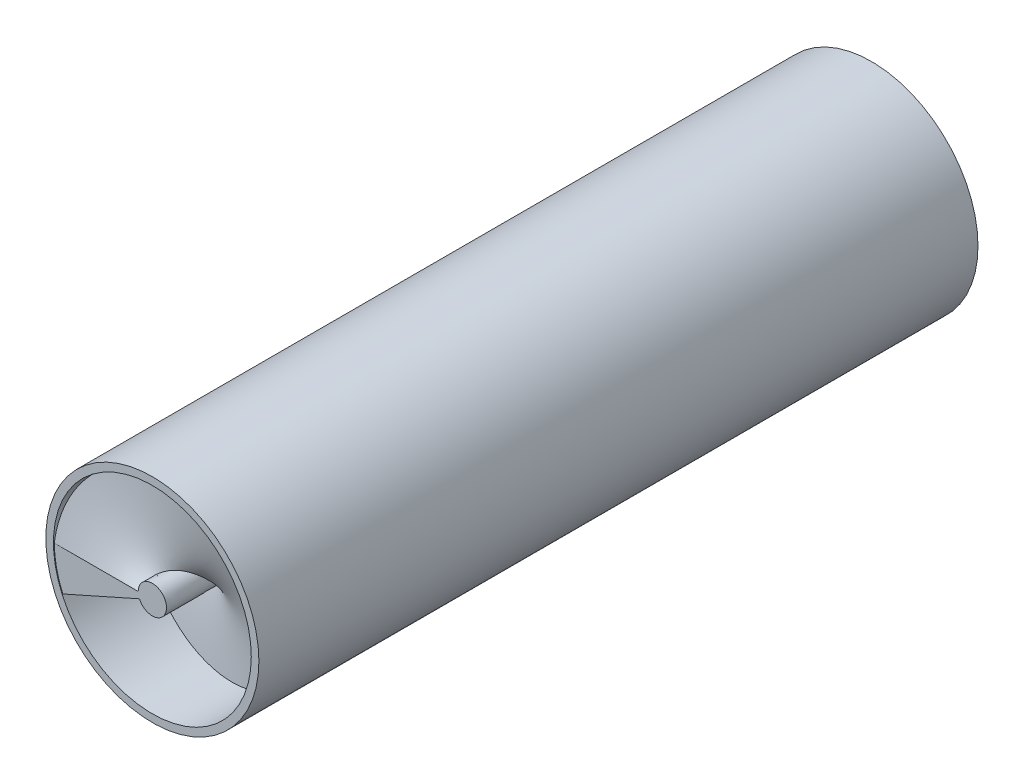
SolidWorks part; units mm, degrees
material "Custom Plastic"
ref_plane "Front Plane" through (0, 0, 0) normal (0, 0, 1) x (1, 0, 0)
ref_plane "Top Plane" through (0, 0, 0) normal (0, 1, 0) x (1, 0, 0)
ref_plane "Right Plane" through (0, 0, 0) normal (1, 0, 0) x (0, 0, -1)
sketch "Sketch2" plane through (0, 0, 0) normal (0, 0, 1) x (1, 0, 0)
  circle A0 centre (0, 0) radius 41.275
  circle A1 centre (0, 0) radius 44.45
  dimension "D1" = 82.55
  dimension "D3" = 88.9
  dimension "D2" = 3.175
extrude "Boss-Extrude2" add sketch "Sketch2" along normal blind 300
sketch "Sketch3" plane through (0, 0, 0) normal (0, 0, 1) x (1, 0, 0)
  circle A0 centre (0, 0) radius 40.9
  dimension "D1" = 81.8
extrude "Boss-Extrude3" add sketch "Sketch3" along normal blind 300 separate body
sketch "Sketch5" plane through (0, 0, 0) normal (0, 0, -1) x (-1, 0, 0)
  circle A0 centre (0, 0) radius 40.9
curve "Helix/Spiral1" pitch 37.5 height 300 radius 40.9 centre (0, 0, 0) axis (0, 0, 1) start towards (-1, 0, 0)
sketch "Sketch8" plane through (0, 0, 0) normal (0, 1, 0) x (1, 0, 0)
  line L1 (-40.9, -300) -> (-5.9, -300)
  line L2 (-40.9, -300) -> (-40.9, -335)
  line L3 (-40.9, -335) -> (-5.9, -335)
  line L4 (-5.9, -300) -> (-5.9, -335)
  dimension "D1" = 35
  dimension "D2" = 35
sweep "Cut-Sweep2" cut profiles "Sketch8" path "Helix/Spiral1" align with end faces yes
